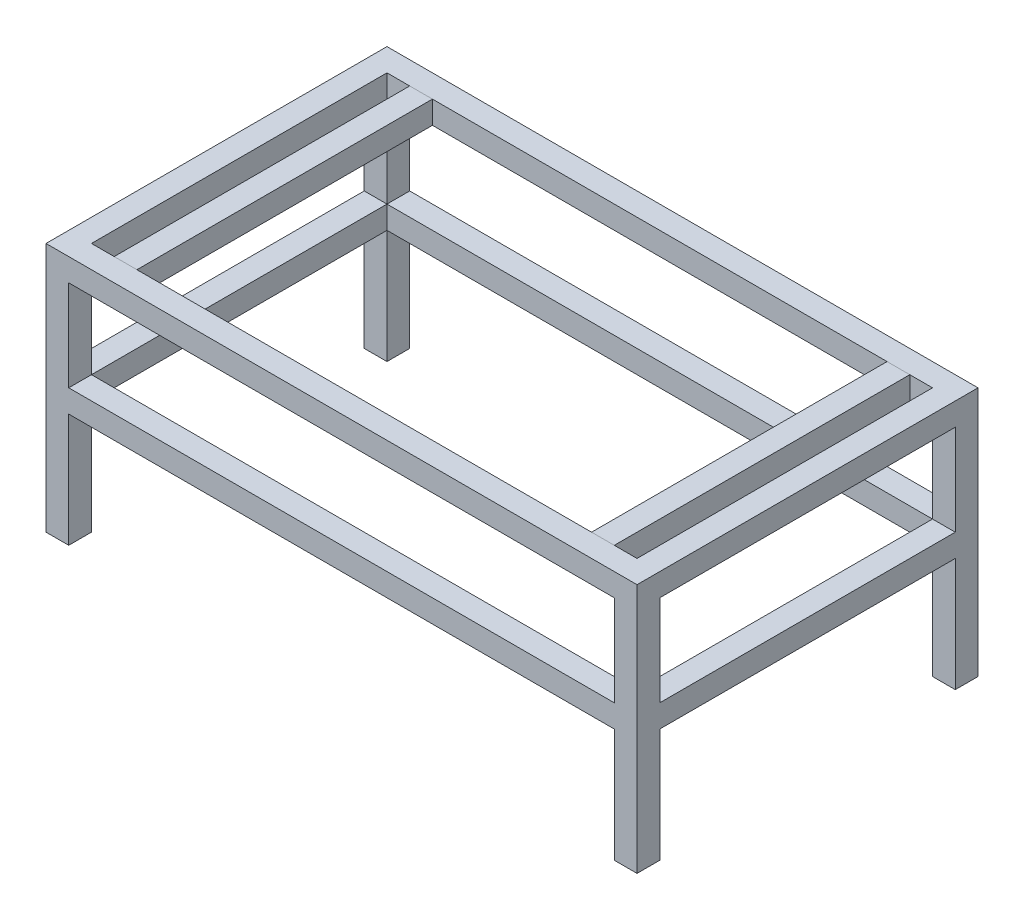
SolidWorks part; units mm, degrees
ref_plane "Plan de face" through (0, 0, 0) normal (0, 0, 1) x (1, 0, 0)
ref_plane "Plan de dessus" through (0, 0, 0) normal (0, 1, 0) x (1, 0, 0)
ref_plane "Plan de droite" through (0, 0, 0) normal (1, 0, 0) x (0, 0, -1)
sketch "Esquisse1" plane through (0, 0, 0) normal (0, 1, 0) x (1, 0, 0)
  line L1 (0, 0) -> (1300, 0)
  line L2 (0, 0) -> (0, 750)
  line L3 (0, 750) -> (1300, 750)
  line L4 (1300, 0) -> (1300, 750)
  line L5 (50, 700) -> (1250, 700)
  line L6 (50, 700) -> (50, 50)
  line L7 (50, 50) -> (1250, 50)
  line L8 (1250, 700) -> (1250, 50)
  dimension "D1" = 1300
  dimension "D2" = 750
  dimension "D3" = 50
  dimension "D4" = 50
  dimension "D5" = 50
  dimension "D6" = 50
extrude "Boss.-Extru.1" add sketch "Esquisse1" against normal blind 550
sketch "Esquisse2" plane through (0, 0, 0) normal (0, 0, 1) x (1, 0, 0)
  line L0 (0, 0) -> (1300, 0) construction
  line L1 (50, -50) -> (1250, -50)
  line L2 (50, -50) -> (50, -250)
  line L3 (50, -250) -> (1250, -250)
  line L4 (1250, -50) -> (1250, -250)
  line L5 (50, -300) -> (1250, -300)
  line L6 (50, -300) -> (50, -550)
  line L7 (50, -550) -> (1250, -550)
  line L8 (1250, -300) -> (1250, -550)
  line L9 (0, -550) -> (1300, -550) construction
  line L10 (1300, -550) -> (1300, 0) construction
  line L11 (0, -550) -> (0, 0) construction
  point P12 (1250, -425)
  dimension "D1" = 50
  dimension "D2" = 50
  dimension "D3" = 200
  dimension "D4" = 0
  dimension "D5" = 50
  dimension "D6" = 50
  dimension "D7" = 50
  dimension "D8" = 50
extrude "Enlèv. mat.-Extru.1" cut sketch "Esquisse2" against normal through all
sketch "Esquisse3" plane through (0, 0, 0) normal (-1, 0, 0) x (0, 0, 1)
  line L0 (-750, -550) -> (0, -550) construction
  line L1 (-700, -50) -> (-50, -50)
  line L2 (-700, -50) -> (-700, -250)
  line L3 (-700, -250) -> (-50, -250)
  line L4 (-50, -50) -> (-50, -250)
  line L5 (-700, -300) -> (-50, -300)
  line L6 (-700, -300) -> (-700, -550)
  line L7 (-700, -550) -> (-50, -550)
  line L8 (-50, -300) -> (-50, -550)
  line L9 (-750, 0) -> (0, 0) construction
  line L10 (0, -550) -> (0, 0) construction
  line L11 (-750, -550) -> (-750, 0) construction
  dimension "D1" = 50
  dimension "D2" = 50
  dimension "D3" = 50
  dimension "D4" = 50
  dimension "D5" = 50
  dimension "D6" = 200
  dimension "D7" = 50
extrude "Enlèv. mat.-Extru.2" cut sketch "Esquisse3" against normal through all
sketch "Esquisse4" plane through (0, 0, 0) normal (0, 1, 0) x (1, 0, 0)
  line L0 (1250, 700) -> (50, 700) construction
  line L1 (100, 700) -> (150, 700)
  line L2 (100, 700) -> (100, 50)
  line L3 (100, 50) -> (150, 50)
  line L4 (150, 700) -> (150, 50)
  line L5 (50, 50) -> (1250, 50) construction
  line L6 (50, 700) -> (50, 50) construction
  line L7 (1150, 700) -> (1200, 700)
  line L8 (1150, 700) -> (1150, 50)
  line L9 (1150, 50) -> (1200, 50)
  line L10 (1200, 700) -> (1200, 50)
  line L11 (1250, 50) -> (1250, 700) construction
  dimension "D1" = 50
  dimension "D2" = 50
  dimension "D3" = 50
  dimension "D4" = 50
extrude "Boss.-Extru.2" add sketch "Esquisse4" against normal blind 50 separate body
